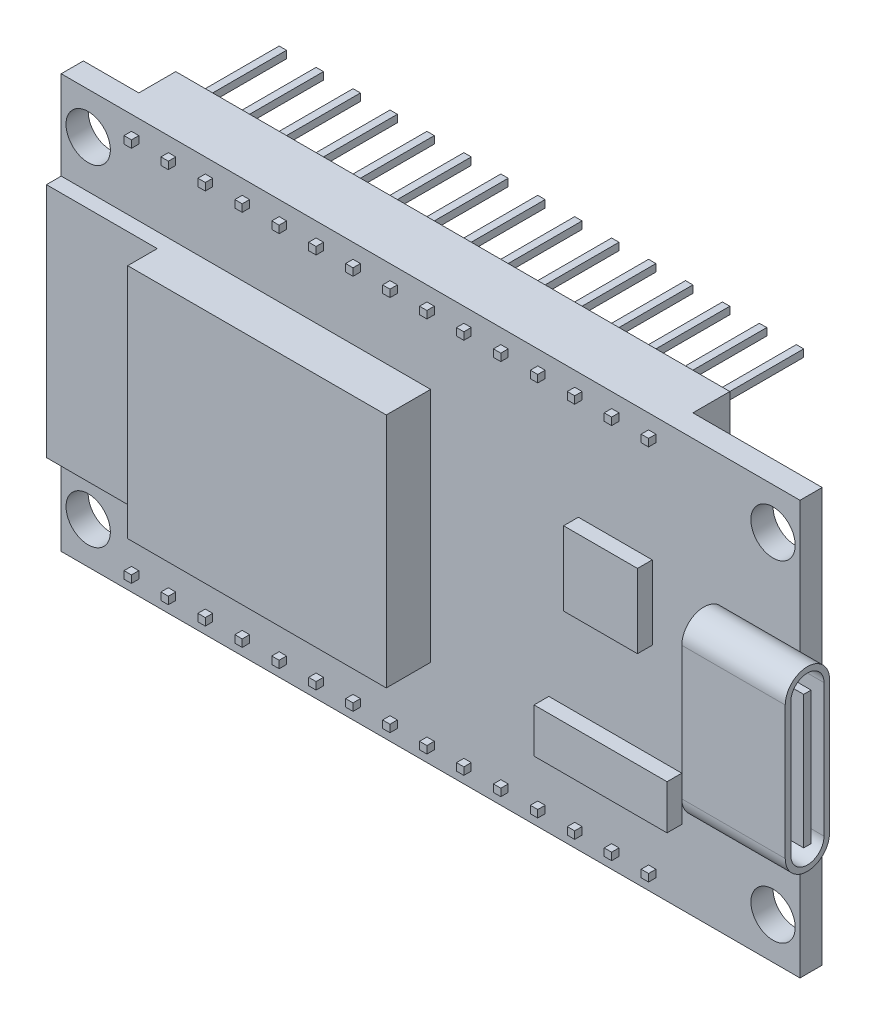
SolidWorks part; units mm, degrees
ref_plane "Front Plane" through (0, 0, 0) normal (0, 0, 1) x (1, 0, 0)
ref_plane "Top Plane" through (0, 0, 0) normal (0, 1, 0) x (1, 0, 0)
ref_plane "Right Plane" through (0, 0, 0) normal (1, 0, 0) x (0, 0, -1)
sketch "Sketch1" plane through (0, 0, 0) normal (0, 0, 1) x (1, 0, 0)
  line L0 (0, 0) -> (0, 14) construction
  line L1 (-25, -14) -> (25, -14)
  line L2 (-25, -14) -> (-25, 14)
  line L3 (-25, 14) -> (25, 14)
  line L4 (25, -14) -> (25, 14)
  line L5 (0, 14) -> (0, -14) construction
  line L6 (0, 0) -> (-25, 0) construction
  line L7 (-25, 0) -> (25, 0) construction
  line L8 (55, 0) -> (-55, 0) construction
  circle A0 centre (23.1744, 11.2012) radius 1.5
  circle A1 centre (23.1744, -11.2012) radius 1.5
  circle A2 centre (-23.1744, 11.2012) radius 1.5
  circle A3 centre (-23.1744, -11.2012) radius 1.5
  point P0 (0, 0)
  dimension "D6" = 3
  dimension "D1" = 50
  dimension "D2" = 28
extrude "Boss-Extrude1" add sketch "Sketch1" along normal mid plane 1.5
ref_plane "Plane1" through (27, 0, 0) normal (1, 0, 0) x (0, 0, -1)
sketch "Sketch5" plane through (27, 0, 0) normal (1, 0, 0) x (0, 0, -1)
  line L0 (0, -14) -> (0, 0)
  line L1 (-0.75, 0) -> (-2.25, 0)
  line L2 (-2.25, -4.5) -> (-2.25, 4.5) construction
  line L3 (-0.75, -14) -> (0.75, -14) construction
  line L4 (0, 0) -> (-0.75, 0)
  line L5 (-3.75, -4.5) -> (-3.75, 4.5)
  line L6 (-0.75, -4.5) -> (-0.75, 4.5)
  arc A0 (-3.75, -4.5) -> (-0.75, -4.5) centre (-2.25, -4.5) ccw
  arc A1 (-0.75, 4.5) -> (-3.75, 4.5) centre (-2.25, 4.5) ccw
  point P8 (-2.25, 0)
  dimension "D1" = 14
  dimension "D2" = 0.75
  dimension "D3" = 1.5
extrude "Boss-Extrude2" add sketch "Sketch5" against normal blind 7 contours L6 A1 L5 A0 region at (27, 0, 3.6263)
sketch "Sketch6" plane through (27, 0, 0) normal (1, 0, 0) x (0, 0, -1)
  line L0 (-2.25, 6) -> (-2.25, -6)
  line L1 (-2.25, -4.5) -> (-2.25, 4.5) construction
  line L2 (-2.5, -4.5) -> (-2, -4.5)
  line L13 (-2.5, -4.5) -> (-2.5, 4.5)
  line L14 (-2.5, 4.5) -> (-2, 4.5)
  line L15 (-2, -4.5) -> (-2, 4.5)
  line L16 (-2.5, -4.5) -> (-2, 4.5) construction
  line L17 (-2.5, 4.5) -> (-2, -4.5) construction
  line L18 (-3.375, -4.5) -> (-3.375, 4.5)
  line L19 (-1.125, -4.5) -> (-1.125, 4.5)
  arc A1 (-0.75, 4.5) -> (-3.75, 4.5) centre (-2.25, 4.5) ccw construction
  arc A2 (-3.75, -4.5) -> (-0.75, -4.5) centre (-2.25, -4.5) ccw construction
  arc A3 (-3.375, -4.5) -> (-1.125, -4.5) centre (-2.25, -4.5) ccw
  arc A4 (-1.125, 4.5) -> (-3.375, 4.5) centre (-2.25, 4.5) ccw
  point P8 (-2.25, 0)
  point P15 (-2.25, 0)
  dimension "D1" = 9
  dimension "D2" = 0.5
sketch "Sketch8" plane through (0, 0, 0.75) normal (0, 0, 1) x (1, 0, 0)
  line L0 (0, 14) -> (0, -14) construction
  line L1 (25, 14) -> (-25, 14) construction
  line L2 (-25, -14) -> (25, -14) construction
  line L3 (0, 8) -> (0, -8)
  line L4 (0, -8) -> (-17.5, -8)
  line L6 (0, 8) -> (-17.5, 8)
  line L7 (-17.5, -8) -> (-17.5, 8)
  line L8 (-25, 14) -> (-25, -14) construction
  line L9 (-17.5, 8) -> (-25, 8)
  line L10 (-17.5, 8) -> (-17.5, 14)
  line L11 (-17.5, 8) -> (-17.5, -8)
  line L12 (-17.5, -8) -> (-25, -8)
  line L13 (-25, 8) -> (-25, -8)
  line L14 (15, 5.5064) -> (15, 7.6756)
  line L19 (15, 0.5064) -> (15, 5.5064)
  line L20 (15, 5.5064) -> (10, 5.5064)
  line L21 (10, 0.5064) -> (10, 5.5064)
  line L24 (10, 0.5064) -> (15, 0.5064)
  line L27 (17, -5.995) -> (8, -5.995)
  line L28 (17, -5.995) -> (17, -8.995)
  line L29 (17, -8.995) -> (8, -8.995)
  line L30 (8, -5.995) -> (8, -8.995)
  line L39 (15, 14) -> (15, 12.75)
  line L40 (11.25, 11.5) -> (11.25, 14)
  line L41 (14.75, 13) -> (15.25, 13)
  line L42 (14.75, 13) -> (14.75, 12.5)
  line L47 (14.75, 12.5) -> (15.25, 12.5)
  line L48 (15.25, 13) -> (15.25, 12.5)
  line L49 (14.75, 13) -> (15.25, 12.5) construction
  line L50 (14.75, 12.5) -> (15.25, 13) construction
  line L51 (13.75, 11.5) -> (16.25, 11.5)
  line L52 (13.75, 11.5) -> (13.75, 14)
  line L53 (13.75, 14) -> (16.25, 14)
  line L54 (16.25, 11.5) -> (16.25, 14)
  line L55 (13.75, 11.5) -> (16.25, 14) construction
  line L56 (13.75, 14) -> (16.25, 11.5) construction
  line L57 (11.25, 11.5) -> (13.75, 11.5)
  line L58 (13.75, 11.5) -> (13.75, 14)
  line L59 (11.25, 14) -> (13.75, 14)
  line L60 (12.25, 13) -> (12.25, 12.5)
  line L61 (12.25, 13) -> (12.75, 13)
  line L62 (12.75, 13) -> (12.75, 12.5)
  line L63 (12.25, 12.5) -> (12.75, 12.5)
  line L64 (8.75, 11.5) -> (8.75, 14)
  line L65 (8.75, 11.5) -> (11.25, 11.5)
  line L66 (11.25, 11.5) -> (11.25, 14)
  line L67 (8.75, 14) -> (11.25, 14)
  line L68 (9.75, 13) -> (9.75, 12.5)
  line L69 (9.75, 13) -> (10.25, 13)
  line L70 (10.25, 13) -> (10.25, 12.5)
  line L71 (9.75, 12.5) -> (10.25, 12.5)
  line L72 (6.25, 11.5) -> (6.25, 14)
  line L73 (6.25, 11.5) -> (8.75, 11.5)
  line L74 (8.75, 11.5) -> (8.75, 14)
  line L75 (6.25, 14) -> (8.75, 14)
  line L76 (7.25, 13) -> (7.25, 12.5)
  line L77 (7.25, 13) -> (7.75, 13)
  line L78 (7.75, 13) -> (7.75, 12.5)
  line L79 (7.25, 12.5) -> (7.75, 12.5)
  line L80 (3.75, 11.5) -> (3.75, 14)
  line L81 (3.75, 11.5) -> (6.25, 11.5)
  line L82 (6.25, 11.5) -> (6.25, 14)
  line L83 (3.75, 14) -> (6.25, 14)
  line L84 (4.75, 13) -> (4.75, 12.5)
  line L85 (4.75, 13) -> (5.25, 13)
  line L86 (5.25, 13) -> (5.25, 12.5)
  line L87 (4.75, 12.5) -> (5.25, 12.5)
  line L88 (1.25, 11.5) -> (1.25, 14)
  line L89 (1.25, 11.5) -> (3.75, 11.5)
  line L90 (3.75, 11.5) -> (3.75, 14)
  line L91 (1.25, 14) -> (3.75, 14)
  line L92 (2.25, 13) -> (2.25, 12.5)
  line L93 (2.25, 13) -> (2.75, 13)
  line L94 (2.75, 13) -> (2.75, 12.5)
  line L95 (2.25, 12.5) -> (2.75, 12.5)
  line L96 (-1.25, 11.5) -> (-1.25, 14)
  line L97 (-1.25, 11.5) -> (1.25, 11.5)
  line L98 (1.25, 11.5) -> (1.25, 14)
  line L99 (-1.25, 14) -> (1.25, 14)
  line L100 (-0.25, 13) -> (-0.25, 12.5)
  line L101 (-0.25, 13) -> (0.25, 13)
  line L102 (0.25, 13) -> (0.25, 12.5)
  line L103 (-0.25, 12.5) -> (0.25, 12.5)
  line L104 (-3.75, 11.5) -> (-3.75, 14)
  line L105 (-3.75, 11.5) -> (-1.25, 11.5)
  line L106 (-1.25, 11.5) -> (-1.25, 14)
  line L107 (-3.75, 14) -> (-1.25, 14)
  line L108 (-2.75, 13) -> (-2.75, 12.5)
  line L109 (-2.75, 13) -> (-2.25, 13)
  line L110 (-2.25, 13) -> (-2.25, 12.5)
  line L111 (-2.75, 12.5) -> (-2.25, 12.5)
  line L112 (-6.25, 11.5) -> (-6.25, 14)
  line L113 (-6.25, 11.5) -> (-3.75, 11.5)
  line L114 (-3.75, 11.5) -> (-3.75, 14)
  line L115 (-6.25, 14) -> (-3.75, 14)
  line L116 (-5.25, 13) -> (-5.25, 12.5)
  line L117 (-5.25, 13) -> (-4.75, 13)
  line L118 (-4.75, 13) -> (-4.75, 12.5)
  line L119 (-5.25, 12.5) -> (-4.75, 12.5)
  line L120 (-8.75, 11.5) -> (-8.75, 14)
  line L121 (-8.75, 11.5) -> (-6.25, 11.5)
  line L122 (-6.25, 11.5) -> (-6.25, 14)
  line L123 (-8.75, 14) -> (-6.25, 14)
  line L124 (-7.75, 13) -> (-7.75, 12.5)
  line L125 (-7.75, 13) -> (-7.25, 13)
  line L126 (-7.25, 13) -> (-7.25, 12.5)
  line L127 (-7.75, 12.5) -> (-7.25, 12.5)
  line L128 (-11.25, 11.5) -> (-11.25, 14)
  line L129 (-11.25, 11.5) -> (-8.75, 11.5)
  line L130 (-8.75, 11.5) -> (-8.75, 14)
  line L131 (-11.25, 14) -> (-8.75, 14)
  line L132 (-10.25, 13) -> (-10.25, 12.5)
  line L133 (-10.25, 13) -> (-9.75, 13)
  line L134 (-9.75, 13) -> (-9.75, 12.5)
  line L135 (-10.25, 12.5) -> (-9.75, 12.5)
  line L136 (-13.75, 11.5) -> (-13.75, 14)
  line L137 (-13.75, 11.5) -> (-11.25, 11.5)
  line L138 (-11.25, 11.5) -> (-11.25, 14)
  line L139 (-13.75, 14) -> (-11.25, 14)
  line L140 (-12.75, 13) -> (-12.75, 12.5)
  line L141 (-12.75, 13) -> (-12.25, 13)
  line L142 (-12.25, 13) -> (-12.25, 12.5)
  line L143 (-12.75, 12.5) -> (-12.25, 12.5)
  line L144 (-16.25, 11.5) -> (-16.25, 14)
  line L145 (-16.25, 11.5) -> (-13.75, 11.5)
  line L146 (-13.75, 11.5) -> (-13.75, 14)
  line L147 (-16.25, 14) -> (-13.75, 14)
  line L148 (-15.25, 13) -> (-15.25, 12.5)
  line L149 (-15.25, 13) -> (-14.75, 13)
  line L150 (-14.75, 13) -> (-14.75, 12.5)
  line L151 (-15.25, 12.5) -> (-14.75, 12.5)
  line L152 (-18.75, 11.5) -> (-18.75, 14)
  line L153 (-18.75, 11.5) -> (-16.25, 11.5)
  line L154 (-16.25, 11.5) -> (-16.25, 14)
  line L155 (-18.75, 14) -> (-16.25, 14)
  line L156 (-17.75, 13) -> (-17.75, 12.5)
  line L157 (-17.75, 13) -> (-17.25, 13)
  line L158 (-17.25, 13) -> (-17.25, 12.5)
  line L159 (-17.75, 12.5) -> (-17.25, 12.5)
  line L160 (-21.25, 11.5) -> (-21.25, 14)
  line L161 (-21.25, 11.5) -> (-18.75, 11.5)
  line L162 (-18.75, 11.5) -> (-18.75, 14)
  line L163 (-21.25, 14) -> (-18.75, 14)
  line L164 (-20.25, 13) -> (-20.25, 12.5)
  line L165 (-20.25, 13) -> (-19.75, 13)
  line L166 (-19.75, 13) -> (-19.75, 12.5)
  line L167 (-20.25, 12.5) -> (-19.75, 12.5)
  line L168 (0, 0) -> (17, 0) construction
  line L169 (17, 0) -> (-25, 0) construction
  line L170 (14.75, -12.5) -> (15.25, -12.5)
  line L171 (15.25, -13) -> (15.25, -12.5)
  line L172 (14.75, -13) -> (15.25, -13)
  line L173 (14.75, -13) -> (14.75, -12.5)
  line L174 (13.75, -14) -> (16.25, -14)
  line L175 (16.25, -11.5) -> (16.25, -14)
  line L176 (13.75, -11.5) -> (16.25, -11.5)
  line L177 (13.75, -11.5) -> (13.75, -14)
  line L178 (11.25, -14) -> (13.75, -14)
  line L179 (13.75, -11.5) -> (13.75, -14)
  line L180 (11.25, -11.5) -> (13.75, -11.5)
  line L181 (11.25, -11.5) -> (11.25, -14)
  line L182 (12.25, -12.5) -> (12.75, -12.5)
  line L183 (12.75, -13) -> (12.75, -12.5)
  line L184 (12.25, -13) -> (12.75, -13)
  line L185 (12.25, -13) -> (12.25, -12.5)
  line L186 (8.75, -14) -> (11.25, -14)
  line L187 (11.25, -11.5) -> (11.25, -14)
  line L188 (8.75, -11.5) -> (11.25, -11.5)
  line L189 (8.75, -11.5) -> (8.75, -14)
  line L190 (9.75, -12.5) -> (10.25, -12.5)
  line L191 (10.25, -13) -> (10.25, -12.5)
  line L192 (9.75, -13) -> (10.25, -13)
  line L193 (9.75, -13) -> (9.75, -12.5)
  line L194 (6.25, -14) -> (8.75, -14)
  line L195 (8.75, -11.5) -> (8.75, -14)
  line L196 (6.25, -11.5) -> (8.75, -11.5)
  line L197 (6.25, -11.5) -> (6.25, -14)
  line L198 (7.25, -12.5) -> (7.75, -12.5)
  line L199 (7.75, -13) -> (7.75, -12.5)
  line L200 (7.25, -13) -> (7.75, -13)
  line L201 (7.25, -13) -> (7.25, -12.5)
  line L202 (3.75, -14) -> (6.25, -14)
  line L203 (6.25, -11.5) -> (6.25, -14)
  line L204 (3.75, -11.5) -> (6.25, -11.5)
  line L205 (3.75, -11.5) -> (3.75, -14)
  line L206 (4.75, -12.5) -> (5.25, -12.5)
  line L207 (5.25, -13) -> (5.25, -12.5)
  line L208 (4.75, -13) -> (5.25, -13)
  line L209 (4.75, -13) -> (4.75, -12.5)
  line L210 (1.25, -14) -> (3.75, -14)
  line L211 (3.75, -11.5) -> (3.75, -14)
  line L212 (1.25, -11.5) -> (3.75, -11.5)
  line L213 (1.25, -11.5) -> (1.25, -14)
  line L214 (2.25, -12.5) -> (2.75, -12.5)
  line L215 (2.75, -13) -> (2.75, -12.5)
  line L216 (2.25, -13) -> (2.75, -13)
  line L217 (2.25, -13) -> (2.25, -12.5)
  line L218 (-1.25, -14) -> (1.25, -14)
  line L219 (1.25, -11.5) -> (1.25, -14)
  line L220 (-1.25, -11.5) -> (1.25, -11.5)
  line L221 (-1.25, -11.5) -> (-1.25, -14)
  line L222 (-0.25, -12.5) -> (0.25, -12.5)
  line L223 (0.25, -13) -> (0.25, -12.5)
  line L224 (-0.25, -13) -> (0.25, -13)
  line L225 (-0.25, -13) -> (-0.25, -12.5)
  line L226 (-3.75, -14) -> (-1.25, -14)
  line L227 (-1.25, -11.5) -> (-1.25, -14)
  line L228 (-3.75, -11.5) -> (-1.25, -11.5)
  line L229 (-3.75, -11.5) -> (-3.75, -14)
  line L230 (-2.75, -12.5) -> (-2.25, -12.5)
  line L231 (-2.25, -13) -> (-2.25, -12.5)
  line L232 (-2.75, -13) -> (-2.25, -13)
  line L233 (-2.75, -13) -> (-2.75, -12.5)
  line L234 (-6.25, -14) -> (-3.75, -14)
  line L235 (-3.75, -11.5) -> (-3.75, -14)
  line L236 (-6.25, -11.5) -> (-3.75, -11.5)
  line L237 (-6.25, -11.5) -> (-6.25, -14)
  line L238 (-5.25, -12.5) -> (-4.75, -12.5)
  line L239 (-4.75, -13) -> (-4.75, -12.5)
  line L240 (-5.25, -13) -> (-4.75, -13)
  line L241 (-5.25, -13) -> (-5.25, -12.5)
  line L242 (-8.75, -14) -> (-6.25, -14)
  line L243 (-6.25, -11.5) -> (-6.25, -14)
  line L244 (-8.75, -11.5) -> (-6.25, -11.5)
  line L245 (-8.75, -11.5) -> (-8.75, -14)
  line L246 (-7.75, -12.5) -> (-7.25, -12.5)
  line L247 (-7.25, -13) -> (-7.25, -12.5)
  line L248 (-7.75, -13) -> (-7.25, -13)
  line L249 (-7.75, -13) -> (-7.75, -12.5)
  line L250 (-11.25, -14) -> (-8.75, -14)
  line L251 (-8.75, -11.5) -> (-8.75, -14)
  line L252 (-11.25, -11.5) -> (-8.75, -11.5)
  line L253 (-11.25, -11.5) -> (-11.25, -14)
  line L254 (-10.25, -12.5) -> (-9.75, -12.5)
  line L255 (-9.75, -13) -> (-9.75, -12.5)
  line L256 (-10.25, -13) -> (-9.75, -13)
  line L257 (-10.25, -13) -> (-10.25, -12.5)
  line L258 (-13.75, -14) -> (-11.25, -14)
  line L259 (-11.25, -11.5) -> (-11.25, -14)
  line L260 (-13.75, -11.5) -> (-11.25, -11.5)
  line L261 (-13.75, -11.5) -> (-13.75, -14)
  line L262 (-12.75, -12.5) -> (-12.25, -12.5)
  line L263 (-12.25, -13) -> (-12.25, -12.5)
  line L264 (-12.75, -13) -> (-12.25, -13)
  line L265 (-12.75, -13) -> (-12.75, -12.5)
  line L266 (-16.25, -14) -> (-13.75, -14)
  line L267 (-13.75, -11.5) -> (-13.75, -14)
  line L268 (-16.25, -11.5) -> (-13.75, -11.5)
  line L269 (-16.25, -11.5) -> (-16.25, -14)
  line L270 (-15.25, -12.5) -> (-14.75, -12.5)
  line L271 (-14.75, -13) -> (-14.75, -12.5)
  line L272 (-15.25, -13) -> (-14.75, -13)
  line L273 (-15.25, -13) -> (-15.25, -12.5)
  line L274 (-18.75, -14) -> (-16.25, -14)
  line L275 (-16.25, -11.5) -> (-16.25, -14)
  line L276 (-18.75, -11.5) -> (-16.25, -11.5)
  line L277 (-18.75, -11.5) -> (-18.75, -14)
  line L278 (-17.75, -12.5) -> (-17.25, -12.5)
  line L279 (-17.25, -13) -> (-17.25, -12.5)
  line L280 (-17.75, -13) -> (-17.25, -13)
  line L281 (-17.75, -13) -> (-17.75, -12.5)
  line L282 (-21.25, -14) -> (-18.75, -14)
  line L283 (-18.75, -11.5) -> (-18.75, -14)
  line L284 (-21.25, -11.5) -> (-18.75, -11.5)
  line L285 (-21.25, -11.5) -> (-21.25, -14)
  line L286 (-20.25, -12.5) -> (-19.75, -12.5)
  line L287 (-19.75, -13) -> (-19.75, -12.5)
  line L288 (-20.25, -13) -> (-19.75, -13)
  line L289 (-20.25, -13) -> (-20.25, -12.5)
  point P6 (0, 0)
  line M175 (25, 14) -> (-25, 14)
  line M176 (-25, 14) -> (-25, -14)
  line M177 (-25, -14) -> (25, -14)
  dimension "D1" = 17.5
  dimension "D2" = 16
  dimension "D3" = 6
  dimension "D4" = 5
  dimension "D5" = 5
  dimension "D6" = 9
  dimension "D7" = 3
  dimension "D8" = 1.25
  dimension "D9" = 0.5
  dimension "D10" = 0.5
  dimension "D11" = 2.5
  dimension "D12" = 15
  dimension "D13" = 15
extrude "Boss-Extrude3" add sketch "Sketch8" against normal blind 4 contours L176 L177 L175 L172 L173 L170 L171 M177 | L180 L181 L177 L184 L185 L182 L183 M177 | L188 L189 L181 L192 L193 L190 L191 M177 | L196 L197 L189 L200 L201 L198 L199 M177 | L204 L205 L197 L208 L209 L206 L207 M177 | L212 L213 L205 L216 L217 L214 L215 M177 | L220 L221 L213 L224 L225 L222 L223 M177 | L228 L229 L221 L232 L233 L230 L231 M177 | L236 L237 L229 L240 L241 L238 L239 M177 | L244 L245 L237 L248 L249 L246 L247 M177 | L252 L253 L245 L256 L257 L254 L255 M177 | L260 L261 L253 L264 L265 L262 L263 M177 | L268 L269 L261 L272 L273 L270 L271 M177 | L276 L277 L269 L280 L281 L278 L279 M177 | L284 L285 L277 L288 L289 L286 L287 M177 | L160 L161 L152 L167 L164 L165 L166 M175 | L159 L10 L153 L144 L157 L158 M175 | L159 L156 L157 L10 L152 L153 M175 | L144 L145 L136 L151 L148 L149 L150 M175 | L136 L137 L128 L143 L140 L141 L142 M175 | L128 L129 L120 L135 L132 L133 L134 M175 | L120 L121 L112 L127 L124 L125 L126 M175 | L112 L113 L104 L119 L116 L117 L118 M175 | L96 L97 L88 L103 L100 L101 L102 M175 | L88 L89 L80 L95 L92 L93 L94 M175 | L80 L81 L72 L87 L84 L85 L86 M175 | L72 L73 L64 L79 L76 L77 L78 M175 | L64 L65 L40 L71 L68 L69 L70 M175 | L40 L57 L52 L63 L60 L61 L62 M175 | L51 L54 L41 L48 L47 L42 L52 M175 | L104 L107 L106 L105 region at (-18.1458, 12.75, 0.75) region at (-16.8542, 12.75, 0.75) region at (-20, 11.5354, 0.75) region at (-16.2146, 12.75, 0.75) region at (-13.7146, 12.75, 0.75) region at (-11.2146, 12.75, 0.75) region at (-8.7146, 12.75, 0.75) region at (-6.2146, 12.75, 0.75) region at (-1.2146, 12.75, 0.75) region at (1.2854, 12.75, 0.75) region at (3.7854, 12.75, 0.75) region at (6.2854, 12.75, 0.75) region at (8.7854, 12.75, 0.75) region at (11.2854, 12.75, 0.75) region at (13.7854, 12.75, 0.75) region at (13.7854, -12.75, 0.75) region at (12.5, -13.9646, 0.75) region at (10, -13.9646, 0.75) region at (7.5, -13.9646, 0.75) region at (5, -13.9646, 0.75) region at (2.5, -13.9646, 0.75) region at (0, -13.9646, 0.75) region at (-2.5, -13.9646, 0.75) region at (-5, -13.9646, 0.75) region at (-7.5, -13.9646, 0.75) region at (-10, -13.9646, 0.75) region at (-12.5, -13.9646, 0.75) region at (-15, -13.9646, 0.75) region at (-17.5, -13.9646, 0.75) region at (-20, -13.9646, 0.75)
extrude "Boss-Extrude4" add sketch "Sketch8<3>" along normal blind 0.5 and the other way blind 10 contours L172 L171 L170 L173
sketch "Sketch8<3>" plane through (0, 0, 0.75) normal (0, 0, 1) x (1, 0, 0) same geometry as "Sketch8"
pattern_linear "LPattern1" count 15 spacing 2.5 along (-1, 0, 0) of "Boss-Extrude4"
mirror "Mirror1" about plane through (0, 0, 0) normal (0, 1, 0) of "LPattern1"
extrude "Boss-Extrude5" add sketch "Sketch8<4>" along normal blind 3 contours L7 L4 L3 L6 region at (-8.75, 0, 0.75)
sketch "Sketch8<4>" plane through (0, 0, 0.75) normal (0, 0, 1) x (1, 0, 0) same geometry as "Sketch8"
extrude "Boss-Extrude6" add sketch "Sketch8<5>" along normal blind 1 contours L12 L7 L9 M176 | L28 L27 L30 L29 | L19 L20 L21 L24 region at (-21.25, 0, 0.75)
sketch "Sketch8<5>" plane through (0, 0, 0.75) normal (0, 0, 1) x (1, 0, 0) same geometry as "Sketch8"
extrude "Cut-Extrude4" cut sketch "Sketch6" against normal blind 6 contours L0 A4 L18 A3 L2 L13 L14 | L19 A4 L0 L14 L15 L2 A3 region at (27, 0, 1.6048) region at (27, 0, 2.8952)
